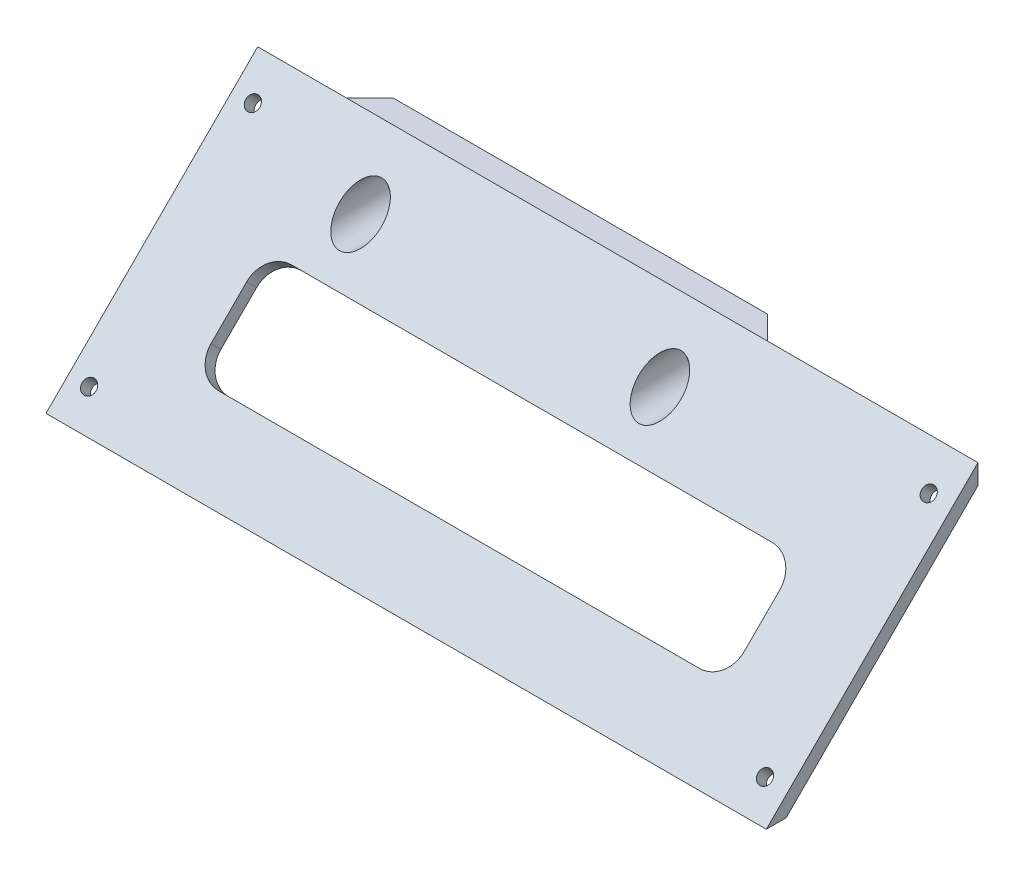
SolidWorks part; units mm, degrees
ref_plane "Front Plane" through (0, 0, 0) normal (0, 0, 1) x (1, 0, 0)
ref_plane "Top Plane" through (0, 0, 0) normal (0, 1, 0) x (1, 0, 0)
ref_plane "Right Plane" through (0, 0, 0) normal (1, 0, 0) x (0, 0, -1)
sketch "Sketch1" plane through (0, 0, 0) normal (0, 0, 1) x (1, 0, 0)
  line L1 (-40, -10) -> (40, -10)
  line L2 (-40, -10) -> (-40, 10)
  line L3 (-40, 10) -> (40, 10)
  line L4 (40, -10) -> (40, 10)
  line L5 (-40, -10) -> (40, 10) construction
  line L6 (-40, 10) -> (40, -10) construction
  point P0 (0, 0)
  dimension "D1" = 20
  dimension "D2" = 80
extrude "Boss-Extrude1" add sketch "Sketch1" along normal blind 5
sketch "Sketch3" plane through (0, 0, 0) normal (1, 0, 0) x (0, 0, -1)
  line L0 (-5, 10) -> (-50.2548, -35.2548)
  line L4 (-50.2548, -35.2548) -> (-46.0122, -35.2548)
  line L5 (-46.0122, -35.2548) -> (-5, 5.7574)
  line L6 (-5, -10) -> (-5, 10) construction
  line L7 (-5, 5.7574) -> (-5, 10)
  dimension "D1" = 3
  dimension "D2" = 45
  dimension "D3" = 64
extrude "Boss-Extrude2" add sketch "Sketch3" against normal blind 64 and the other way blind 90
sketch "Sketch4" plane through (0, 5.3787, 5.3787) normal (0, -0.7071, -0.7071) x (1, 0, 0)
  line L0 (-64, 57.4645) -> (-64, -0.5355) construction
  line L1 (70, 44.4645) -> (-44, 44.4645)
  line L2 (70, 44.4645) -> (70, 22.4645)
  line L3 (70, 22.4645) -> (-44, 22.4645)
  line L4 (-44, 44.4645) -> (-44, 22.4645)
  line L5 (70, 44.4645) -> (-44, 22.4645) construction
  line L6 (70, 22.4645) -> (-44, 44.4645) construction
  line L7 (90, 57.4645) -> (90, -0.5355) construction
  line L8 (90, 57.4645) -> (-64, 57.4645) construction
  point P0 (13, 33.4645)
  point P5 (0, 0)
  dimension "D1" = 20
  dimension "D2" = 20
  dimension "D3" = 13
  dimension "D4" = 22
extrude "Cut-Extrude2" cut sketch "Sketch4" against normal through all
chamfer "Chamfer1" distance 5 angle 45 2 edges at (40, 7.8787, 5) (-40, 7.8787, 5)
chamfer "Chamfer2" distance 11.3 angle 90 1 edges at (0, 5.7574, 5) first distance on face at (13, -18.2843, 29.0416)
chamfer "Chamfer4" distance 5 angle 65 1 edges at (0, -2.2329, 12.9903) first distance on face at (0, -6.1165, 9.1068)
ref_plane "Plane1" through (0, 0, 5) normal (0, 0, -1) x (-1, 0, 0)
sketch "Sketch2" plane through (0, 0, 0) normal (0, 0, 1) x (1, 0, 0)
  circle A0 centre (-32, 0) radius 2.3
  circle A1 centre (32, 0) radius 2.3
  dimension "D3" = 4.6
  dimension "D1" = 32
  dimension "D2" = 32
extrude "Cut-Extrude1" cut sketch "Sketch2" against normal through all and the other way through all
sketch "Sketch5" plane through (0, 0, 5) normal (0, 0, -1) x (-1, 0, 0)
  circle A0 centre (-32, 0) radius 4.5
  circle A1 centre (32, 0) radius 4.5
  dimension "D1" = 9
extrude "Cut-Extrude3" cut sketch "Sketch5" against normal through all
sketch "Sketch6" plane through (0, 7.5, 7.5) normal (0, 0.7071, 0.7071) x (1, 0, 0)
  circle A0 centre (-59.55, -4.2145) radius 1.5
  circle A1 centre (-59.55, -53.7145) radius 1.5
  circle A2 centre (84.95, -53.7145) radius 1.5
  circle A3 centre (84.95, -4.2145) radius 1.5
  dimension "D1" = 3
extrude "Cut-Extrude4" cut sketch "Sketch6" against normal blind 5
fillet "Fillet2" radius 5.6 4 edges at (70, -9.4454, 22.3241) (70, -25.0018, 37.8805) (-44, -25.0018, 37.8805) (-44, -9.4454, 22.3241)
